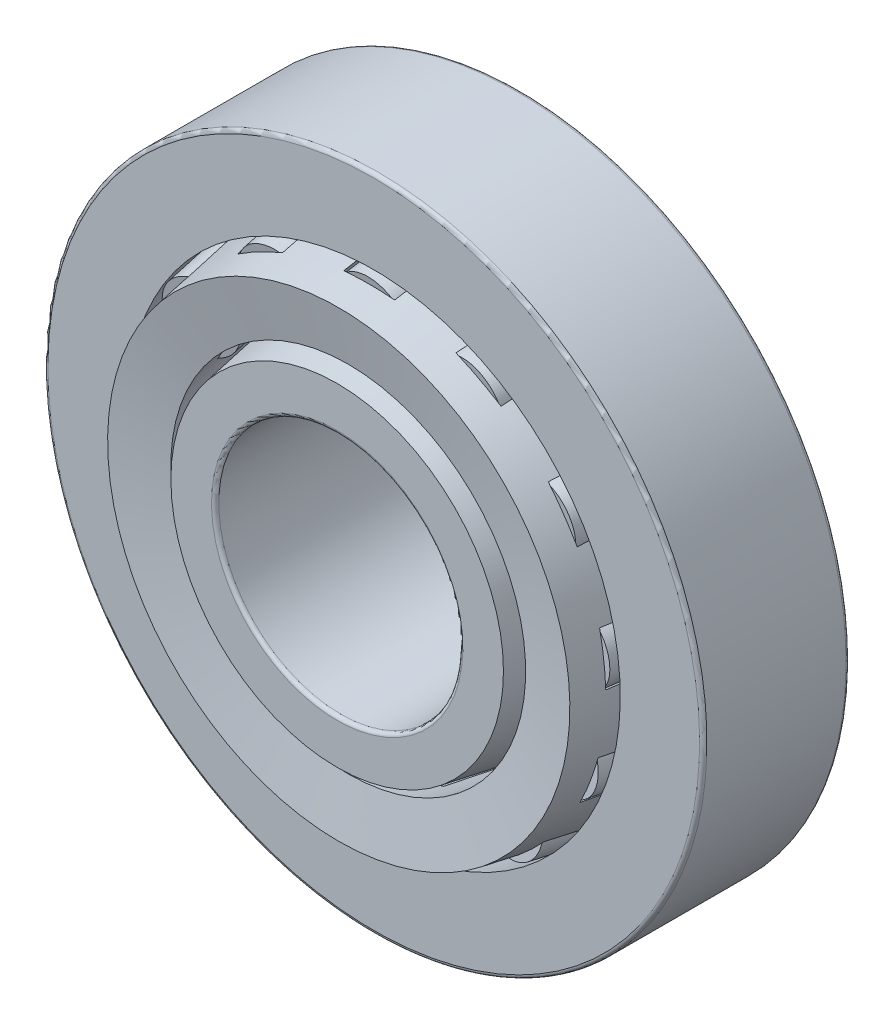
SolidWorks part; units mm, degrees
ref_plane "Front Plane" through (0, 0, 0) normal (0, 0, 1) x (1, 0, 0)
ref_plane "Top Plane" through (0, 0, 0) normal (0, 1, 0) x (1, 0, 0)
ref_plane "Right Plane" through (0, 0, 0) normal (1, 0, 0) x (0, 0, -1)
sketch "Sketch1" plane through (0, 0, 0) normal (1, 0, 0) x (0, 0, -1)
  line L0 (-7.1437, 0) -> (7.1437, 0) construction
  line L1 (0, 0) -> (0, 21.4312) construction
  line L2 (-7.1437, 7.9375) -> (7.1437, 7.9375) construction
  line L3 (7.1437, 7.9375) -> (7.1437, 13.335) construction
  line L4 (7.1437, 13.335) -> (-7.1437, 10.8157) construction
  line L5 (-7.1437, 10.8157) -> (-7.1437, 7.9375) construction
  line L7 (-4.7625, 21.4312) -> (4.7625, 21.4312)
  line L8 (4.7625, 21.4312) -> (4.7625, 17.7133)
  line L9 (4.7625, 17.7133) -> (-4.7625, 16.0337)
  line L10 (-4.7625, 16.0337) -> (-4.7625, 21.4312)
  line L12 (5.8152, 17.8989) -> (6.6357, 13.2454) construction
  line L13 (-6.3232, 10.9604) -> (-7.1438, 15.6139) construction
  line L14 (-7.1437, 10.8157) -> (-6.3232, 10.9604) construction
  line L15 (-7.1437, 10.8157) -> (6.6357, 13.2454) construction
  line L20 (-7.1437, -10.8157) -> (6.6357, -13.2454) construction
  line L21 (-7.1437, -10.8157) -> (-6.3232, -10.9604) construction
  line L22 (-6.3232, -10.9604) -> (-7.1438, -15.6139) construction
  line L23 (5.8152, -17.8989) -> (6.6357, -13.2454) construction
  line L24 (-7.1437, -10.8157) -> (-7.1437, -7.9375) construction
  line L25 (7.1437, -13.335) -> (-7.1437, -10.8157) construction
  line L26 (7.1437, -7.9375) -> (7.1437, -13.335) construction
  line L27 (-7.1437, -7.9375) -> (7.1437, -7.9375) construction
  line L28 (-4.7625, -16.0337) -> (-4.7625, -21.4312) construction
  line L29 (4.7625, -17.7133) -> (-4.7625, -16.0337) construction
  line L30 (4.7625, -21.4312) -> (4.7625, -17.7133) construction
  line L31 (-4.7625, -21.4312) -> (4.7625, -21.4312) construction
  point P5 (0, 7.9375)
  point P37 (0, -7.9375)
  dimension "D1" = 100
  dimension "Width" = 9.525
  dimension "OD" = 42.8625
  dimension "Shaft Dia" = 15.875
  dimension "D2" = 13.4938
  dimension "D3" = 5.3975
  dimension "Cage Width" = 13.7795
  dimension "Inner Ring Width" = 14.2875
revolve "Revolve1" add sketch "Sketch1" angle 360 about L0
sketch "Sketch5" plane through (0, 0, 0) normal (1, 0, 0) x (0, 0, -1)
  line L0 (7.1437, 13.335) -> (-7.1437, 10.8157) construction
  line L1 (7.1437, 13.335) -> (-7.1437, 10.8157)
  line L2 (-7.1437, 10.8157) -> (-7.1437, 7.9375)
  line L3 (-7.1437, 7.9375) -> (7.1437, 7.9375)
  line L4 (7.1437, 7.9375) -> (7.1437, 13.335)
revolve "Revolve4" add sketch "Sketch5" angle 360 about L0
sketch "Sketch2" plane through (0, 0, 0) normal (1, 0, 0) x (0, 0, -1)
  line L0 (-7.0412, 15.0322) -> (-6.4258, 11.5421)
  line L1 (4.7625, 17.1135) -> (5.9178, 17.3172)
  line L2 (-6.4258, 11.5421) -> (4.7625, 13.5149)
  line L3 (5.8152, 17.8989) -> (6.6357, 13.2454) construction
  line L4 (4.7625, 13.5149) -> (4.7625, 17.1135) construction
  line L5 (4.7625, 17.1135) -> (-7.0412, 15.0322)
  line L6 (4.7625, 17.7133) -> (-4.7625, 16.0337) construction
  line L7 (7.1437, 13.335) -> (-7.1437, 10.8157) construction
  line L8 (-7.1438, 15.6139) -> (4.7625, 17.7133) construction
  line L9 (-6.3232, 10.9604) -> (6.6357, 13.2454) construction
  line L10 (5.9178, 17.3172) -> (6.5332, 13.8271)
  line L11 (-7.1438, 15.6139) -> (-7.0412, 15.0322) construction
  line L12 (4.7625, -21.4312) -> (4.7625, 21.4312) construction
  line L13 (4.7625, 21.4312) -> (4.7625, 17.7133) construction
  line L14 (6.5332, 13.8271) -> (4.7625, 13.5149)
  line L15 (-6.4258, 11.5421) -> (-6.3232, 10.9604) construction
  line L16 (0, 0) -> (-7.1438, 0) construction
  line L17 (-7.1437, 10.8157) -> (-7.1437, -10.8157) construction
  line L18 (-6.4258, -11.5421) -> (-6.3232, -10.9604) construction
  line L19 (-7.1438, -15.6139) -> (-7.0412, -15.0322) construction
  line L20 (-6.3232, -10.9604) -> (6.6358, -13.2454) construction
  line L21 (-7.1438, -15.6139) -> (4.7625, -17.7133) construction
  line L22 (4.7625, -13.5149) -> (4.7625, -17.1135) construction
  line L23 (6.5332, -13.8271) -> (4.7625, -13.5149) construction
  line L24 (5.9178, -17.3172) -> (6.5332, -13.8271) construction
  line L25 (4.7625, -17.1135) -> (-7.0412, -15.0322) construction
  line L26 (-6.4258, -11.5421) -> (4.7625, -13.5149) construction
  line L27 (4.7625, -17.1135) -> (5.9178, -17.3172) construction
  line L28 (-7.0412, -15.0322) -> (-6.4258, -11.5421) construction
  dimension "D1" = 4.7252
  dimension "D2" = 3.5439
revolve "Revolve2" add sketch "Sketch2" angle 360 about L0
sketch "Sketch3" plane through (0, 0, 0) normal (1, 0, 0) x (0, 0, -1)
  line L0 (-6.7335, 13.2871) -> (4.7625, 15.3142) construction
  line L1 (-7.0412, 15.0322) -> (-6.4258, 11.5421) construction
  line L2 (4.7625, 13.5149) -> (4.7625, 17.1135) construction
  line L3 (-4.7625, 13.6347) -> (-5.1728, 15.9614)
  line L5 (-5.1728, 15.9614) -> (4.3522, 17.6409)
  line L6 (4.3522, 17.6409) -> (4.7625, 15.3142)
  line L7 (4.7625, 15.3142) -> (-4.7625, 13.6347)
  line L11 (-6.7335, 13.2871) -> (-4.7625, 13.6347) construction
  line L12 (-4.7625, 21.4312) -> (-4.7625, -21.4312) construction
  line L13 (-6.7335, 13.2871) -> (-4.7625, 13.6347) construction
revolve "Cut-Revolve1" cut sketch "Sketch3" angle 360 about L0
sketch "Sketch4" plane through (0, 0, 0) normal (1, 0, 0) x (0, 0, -1)
  line L0 (-5.1507, 15.8363) -> (4.3743, 17.5159)
  line L1 (4.3743, 17.5159) -> (4.7625, 15.3142)
  line L2 (4.7625, 15.3142) -> (-4.7625, 13.6347)
  line L3 (-4.7625, 13.6347) -> (-6.7335, 13.2871) construction
  line L4 (-4.7625, 13.6347) -> (-5.1507, 15.8363)
  line L5 (-6.7335, 13.2871) -> (-4.7625, 13.6347) construction
  line L6 (4.7625, 15.3142) -> (-4.7625, 13.6347) construction
  line L7 (4.7625, 17.7133) -> (-4.7625, 16.0337) construction
  line L8 (0, 0) -> (-7.1437, 0) construction
  line L9 (-7.1437, 0) -> (7.1437, 0) construction
  line L10 (-6.7335, -13.2871) -> (-4.7625, -13.6347) construction
  line L11 (-4.7625, -13.6347) -> (-6.7335, -13.2871) construction
  line L12 (-4.7625, -13.6347) -> (-5.1507, -15.8363) construction
  line L13 (4.7625, -15.3142) -> (-4.7625, -13.6347) construction
  line L14 (4.3743, -17.5159) -> (4.7625, -15.3142) construction
  line L15 (-5.1507, -15.8363) -> (4.3743, -17.5159) construction
  dimension "D1" = 0.127
revolve "Revolve3" add sketch "Sketch4" angle 360 about L0
sketch "Sketch7" plane through (0, 0, 0) normal (0, 0, 1) x (1, 0, 0)
  line L0 (0, 0) -> (-1.9433, 11.6961) construction
  line L1 (0, 0) -> (1.9433, 11.6961) construction
  ellipse E0 centre (0, 13.6347) end of major axis (-2.2356, 13.6347) minor radius 2.2017 construction
  dimension "D1" = 18.867
ref_axis "Axis1" through (0, 0, -7.1437) along (0, 0, 1)
pattern_circular "CirPattern2" count 13 over 360 about axis through (0, 0, -7.1437) along (0, 0, 1) of bodies 403
pattern_circular "CirPattern1" count 13 over 360 about axis through (0, 0, -7.1437) along (0, 0, 1) of "Cut-Revolve1"
fillet "Fillet1" radius 0.2381 2 edges at (0, -21.4312, -4.7625) (0, -21.4312, 4.7625)
fillet "Fillet2" radius 0.2381 2 edges at (0, -7.9375, -7.1437) (0, -7.9375, 7.1437)
sketch "Sketch6" plane through (0, 0, 0) normal (1, 0, 0) x (0, 0, -1)
  line L0 (-41.5662, 21.4312) -> (-41.5662, 16.0338)
  line L1 (-41.5662, 16.0338) -> (-32.0412, 17.7133)
  line L2 (-32.0412, 17.7133) -> (-32.0412, 21.4312)
  line L3 (-32.0412, 21.4312) -> (-41.5662, 21.4312)
  line L4 (-4.7625, 21.4312) -> (4.7625, 21.4312) construction
  line L5 (4.7625, 21.4312) -> (4.7625, 17.7133) construction
  line L6 (4.7625, 17.7133) -> (-4.7625, 16.0337) construction
  line L7 (-7.0412, -15.0322) -> (-7.0412, 15.0322) construction
  dimension "D1" = 25
revolve "Revolve5" [suppressed] add sketch "Sketch6" angle 360 about L0
fillet "Fillet3" [suppressed] radius 0.2381
delete or keep bodies "Body-Delete1" [suppressed] type delete bodies bodies 399
equation "\"D3@Sketch1\" = \"D2@Sketch1\"/2.5"
equation "\"D2@Sketch2\" = \"D1@Sketch2\"*.75"
equation "\"D1@Fillet1\"= \"Width@Sketch1\" * .025"
equation "\"D1@Fillet2\" = \"D1@Fillet1\""
equation "\"D1@Fillet3\" = \"D1@Fillet1\""
equation "\"Rollers@CirPattern2\"=(360/\"D1@Sketch7\")/1.50"
equation "\"D1@CirPattern1\"=\"Rollers@CirPattern2\""
